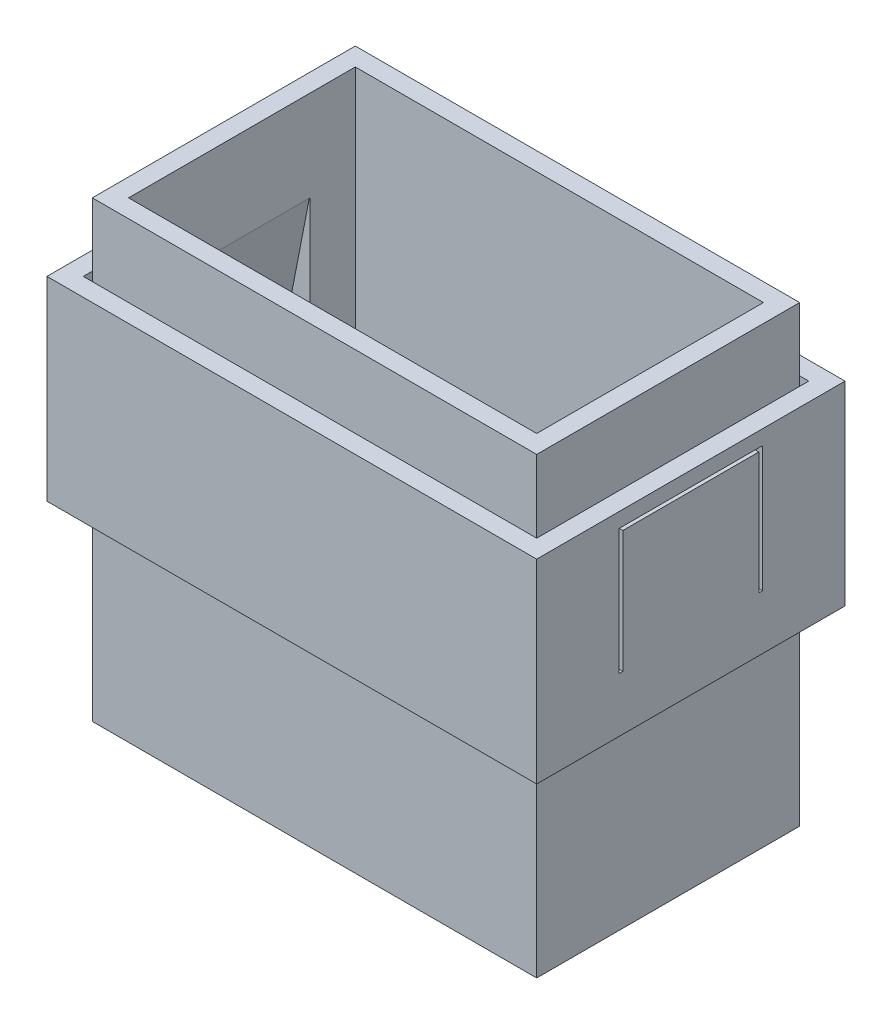
SolidWorks part; units mm, degrees
note: '?' marks a value the reader was unsure of.
ref_plane "Alzado" through (0, 0, 0) normal (0, 0, 1) x (1, 0, 0)
ref_plane "Planta" through (0, 0, 0) normal (0, 1, 0) x (1, 0, 0)
ref_plane "Vista lateral" through (0, 0, 0) normal (1, 0, 0) x (0, 0, -1)
sketch "Croquis1" plane through (0, 0, 0) normal (0, 1, 0) x (1, 0, 0)
  line L1 (-22.5, 12.5) -> (22.5, 12.5)
  line L2 (-22.5, 12.5) -> (-22.5, -12.5)
  line L3 (-22.5, -12.5) -> (22.5, -12.5)
  line L4 (22.5, 12.5) -> (22.5, -12.5)
  line L5 (-22.5, 12.5) -> (22.5, -12.5) construction
  line L6 (-22.5, -12.5) -> (22.5, 12.5) construction
  line L7 (-24.5, -14.5) -> (24.5, -14.5)
  line L8 (-24.5, -14.5) -> (-24.5, 14.5)
  line L9 (-24.5, 14.5) -> (24.5, 14.5)
  line L10 (24.5, -14.5) -> (24.5, 14.5)
  line L11 (-24.5, -14.5) -> (24.5, 14.5) construction
  line L12 (-24.5, 14.5) -> (24.5, -14.5) construction
  point P0 (0, 0)
  point P6 (0, 0)
  dimension "D1" = 45
  dimension "D2" = 25
  dimension "D3" = 2
  dimension "D4" = 2
extrude "Saliente-Extruir1" add sketch "Croquis1" along normal mid plane 50
sketch "Croquis2" plane through (0, 0, 0) normal (0, 1, 0) x (1, 0, 0)
  line L0 (24.5, -14.5) -> (24.5, 14.5) construction
  line L1 (-25, -15) -> (25, -15)
  line L2 (-25, -15) -> (-25, 15)
  line L3 (-25, 15) -> (25, 15)
  line L4 (25, -15) -> (25, 15)
  line L5 (-25, -15) -> (25, 15) construction
  line L6 (-25, 15) -> (25, -15) construction
  line L7 (24.5, 14.5) -> (-24.5, 14.5) construction
  line L9 (-27, -17) -> (27, -17)
  line L10 (-27, -17) -> (-27, 17)
  line L11 (-27, 17) -> (27, 17)
  line L12 (27, -17) -> (27, 17)
  line L13 (-27, -17) -> (27, 17) construction
  line L14 (-27, 17) -> (27, -17) construction
  point P0 (0, 0)
  point P10 (0, 0)
  dimension "D1" = 0.5
  dimension "D2" = 0.5
  dimension "D3" = 2
  dimension "D4" = 2
extrude "Saliente-Extruir2" add sketch "Croquis2" along normal mid plane 35 separate body
sketch "Croquis3" plane through (22.5, 0, 0) normal (-1, 0, 0) x (0, 0, 1)
  line L0 (0, 20.1627) -> (0, -22.7075) construction
  line L1 (17, 17.5) -> (-21.8994, 17.5) construction
  line L2 (17, 17.5) -> (-17, 17.5) construction
  line L4 (-7.5, 15) -> (7.5, 15)
  line L5 (-7.5, 15) -> (-7.5, 5)
  line L6 (-7.5, 5) -> (7.5, 5)
  line L7 (7.5, 15) -> (7.5, 5)
  line L8 (-7.5, 15) -> (7.5, 5) construction
  line L9 (-7.5, 5) -> (7.5, 15) construction
  point P7 (0, 10)
  dimension "D1" = 10
  dimension "D2" = 15
  dimension "D3" = 10
extrude "Cortar-Extruir1" cut sketch "Croquis3" against normal up to next and the other way up to next
ref_plane "Plano1" through (24.5445, 4.771, 0) normal (0.9816, 0.1908, 0) x (0, 0, -1)
ref_axis "Eje1" through (25, 2.4277, 15) along (0, 0, -1)?
sketch "Croquis4" plane through (24.5445, 4.771, 0) normal (0.9816, 0.1908, 0) x (0, 0, -1)
  line L0 (-7.5, 10.4312) -> (7.5, 10.4312) construction
  line L5 (-7.5, 10.4312) -> (7.5, 10.4312)
  line L7 (-7.5, -2.3871) -> (-7.5, 10.4312)
  line L10 (7.5, 10.4312) -> (7.5, -2.3871)
  line L11 (7.5, -2.3871) -> (-7.5, -2.3871)
  line L12 (-15, -2.3871) -> (15, -2.3871) construction
  line L13 (7.5, 10.4312) -> (7.5, 0.6149) construction
  line L14 (-7.5, 0.6149) -> (-7.5, 10.4312) construction
  point P4 (0, 0)
extrude "Saliente-Extruir3" add sketch "Croquis4" along normal up to next separate body
sketch "Croquis6" plane through (25, 0, 0) normal (-1, 0, 0) x (0, 0, 1)
  line L0 (7.5, 2.4277) -> (-7.5, 2.4277) construction
  line L1 (-7.9, 15.886) -> (7.9, 15.886)
  line L3 (-7.5, 15.486) -> (7.5, 15.486)
  line L5 (-7.9, 2.0277) -> (-7.5, 2.0277)
  line L6 (-7.9, 2.0277) -> (-7.9, 15.886)
  line L8 (-7.5, 2.0277) -> (-7.5, 15.486)
  line L10 (7.9, 15.886) -> (7.9, 2.0277)
  line L11 (7.9, 2.0277) -> (7.5, 2.0277)
  line L12 (7.5, 15.486) -> (7.5, 2.0277)
  line L13 (-7.5, 2.4277) -> (-7.5, 15.0105) construction
  line L14 (7.5, 15.0105) -> (7.5, 2.4277) construction
  line L15 (7.5, 15.486) -> (-7.5, 15.486) construction
  point P6 (0, 0)
  dimension "D1" = 0.4
  dimension "D2" = 0.4
  dimension "D3" = 0.4
  dimension "D4" = 0.4
  dimension "D5" = 0.4
extrude "Cortar-Extruir2" cut sketch "Croquis6" against normal up to next (2 mm away)
mirror "Simetría1" about plane through (0, 0, 0) normal (1, 0, 0) of "Cortar-Extruir2", "Saliente-Extruir3"
sketch "Croquis7" plane through (0, 0, 17) normal (0, 0, 1) x (1, 0, 0)
  line L0 (-27, 2.0277) -> (-25, 2.0277) construction
  line L1 (-27, -3.9723) -> (27, -3.9723)
  line L2 (-27, -3.9723) -> (-27, -17.5)
  line L3 (-27, -17.5) -> (27, -17.5)
  line L4 (27, -3.9723) -> (27, -17.5)
  line L5 (-27, 17.5) -> (-27, -17.5) construction
  line L6 (-27, -17.5) -> (27, -17.5) construction
  line L7 (27, 17.5) -> (27, -17.5) construction
  dimension "D1" = 6
extrude "Cortar-Extruir3" cut sketch "Croquis7" against normal through all both and the other way through all
